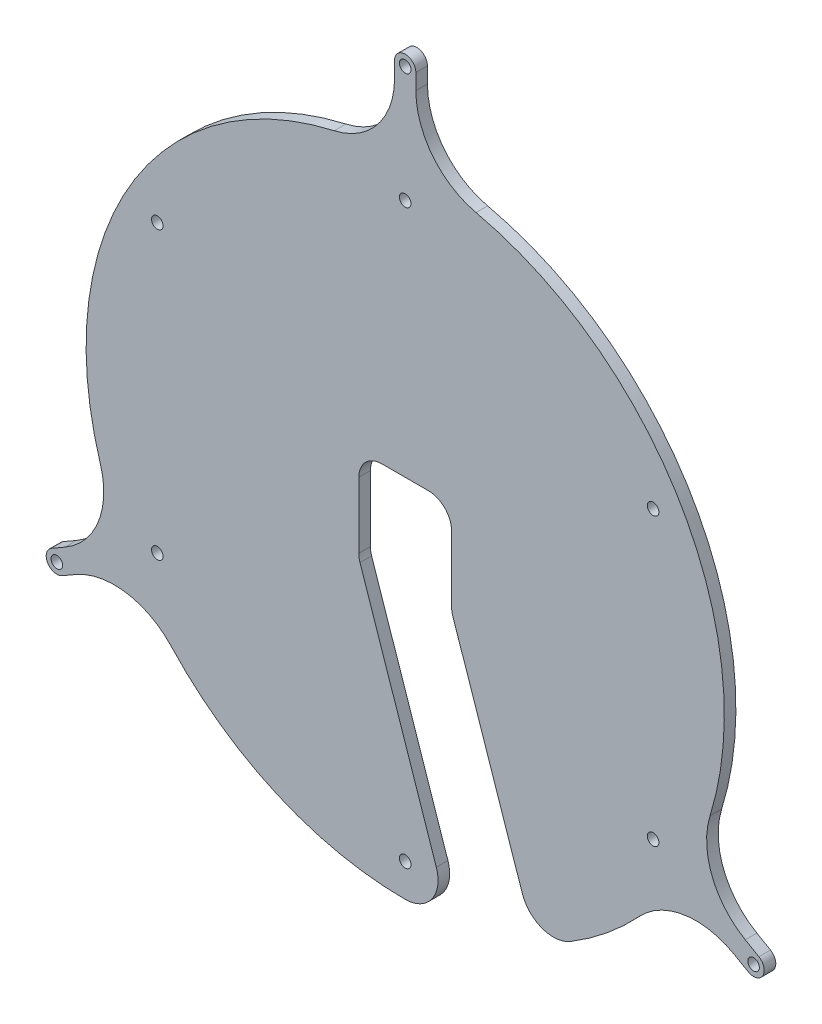
SolidWorks part; units mm, degrees
material "Oak"
ref_plane "Front Plane" through (0, 0, 0) normal (0, 0, 1) x (1, 0, 0)
ref_plane "Top Plane" through (0, 0, 0) normal (0, 1, 0) x (1, 0, 0)
ref_plane "Right Plane" through (0, 0, 0) normal (1, 0, 0) x (0, 0, -1)
sketch "Sketch1" plane through (0, 0, 0) normal (0, 0, 1) x (1, 0, 0)
  line L0 (0, 0) -> (64.0859, 37) construction
  line L1 (0, 0) -> (0, 74) construction
  circle A0 centre (0, 0) radius 82.5
  circle A1 centre (0, 0) radius 74 construction
  circle A2 centre (0, 74) radius 1.5
  circle A3 centre (0, -74) radius 1.5
  circle A4 centre (64.0859, 37) radius 1.5
  circle A5 centre (64.0859, -37) radius 1.5
  circle A6 centre (-64.0859, -37) radius 1.5
  circle A7 centre (-64.0859, 37) radius 1.5
  dimension "D1" = 165
  dimension "D3" = 3
  dimension "D4" = 148
  dimension "D2" = 60
extrude "Boss-Extrude1" add sketch "Sketch1" along normal blind 3
sketch "Sketch2" plane through (0, 0, 3) normal (0, 0, 1) x (1, 0, 0)
  line L0 (12, -12) -> (30.2754, -66.0248)
  line L2 (-12, -12) -> (-12, 12)
  line L3 (-12, 12) -> (12, 12)
  line L4 (12, -12) -> (12, 12)
  line L5 (-12, -12) -> (12, 12) construction
  line L6 (-12, 12) -> (12, -12) construction
  line L7 (-12, -12) -> (8.0518, -71.2763)
  arc A0 (30.2754, -66.0248) -> (42.7296, -70.5722) centre (38.3271, -63.3011) ccw
  arc A1 (0, -82.5) -> (8.0518, -71.2763) centre (0, -74) ccw
  arc A2 (0, -82.5) -> (42.7296, -70.5722) centre (0, 0) ccw
  circle A3 centre (0, 0) radius 82.5 construction
  point P0 (0, 0)
  dimension "D1" = 24
extrude "Cut-Extrude1" cut sketch "Sketch2" against normal through all
fillet "Fillet1" radius 6 4 edges at (-12, -12, 1.5) (-12, 12, 1.5) (12, 12, 1.5) (12, -12, 1.5)
sketch "Sketch3" plane through (0, 0, 3) normal (0, 0, 1) x (1, 0, 0)
  line L0 (2.75, 104) -> (2.75, 99.9434)
  line L2 (-2.75, 99.9434) -> (-2.75, 104)
  circle A0 centre (0, 104) radius 1.5
  arc A1 (2.75, 104) -> (-2.75, 104) centre (0, 104) ccw
  arc A2 (2.75, 99.9434) -> (18.311, 80.4423) centre (22.75, 99.9434) ccw
  arc A3 (-18.311, 80.4423) -> (-2.75, 99.9434) centre (-22.75, 99.9434) ccw
  arc A4 (18.311, 80.4423) -> (-18.311, 80.4423) centre (0, 0) ccw
  arc A5 (42.7296, -70.5722) -> (0, -82.5) centre (0, 0) ccw construction
  circle A6 centre (0, 74) radius 1.5 construction
  dimension "D1" = 2.75
  dimension "D3" = 20
  dimension "D2" = 104
extrude "Boss-Extrude2" add sketch "Sketch3" against normal up to surface (3 mm away) up to face at (3.3147, -12.4054, 0)
ref_axis "Axis1" through (0, 0, 3.15) along (0, 0, -1)
pattern_circular "CirPattern1" count 3 over 360 about axis through (0, 0, 3.15) along (0, 0, -1) of "Boss-Extrude2"
